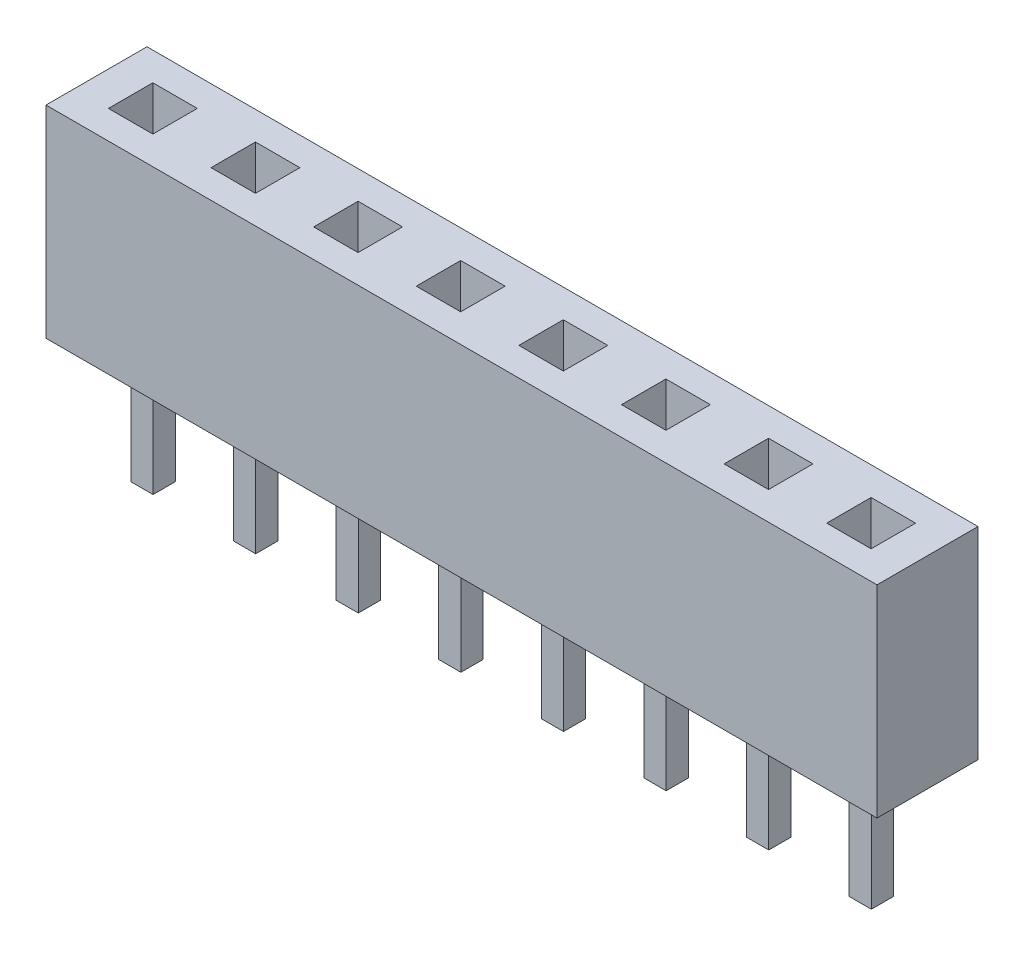
SolidWorks part; units mm, degrees
ref_plane "Front Plane" through (0, 0, 0) normal (0, 0, 1) x (1, 0, 0)
ref_plane "Top Plane" through (0, 0, 0) normal (0, 1, 0) x (1, 0, 0)
ref_plane "Right Plane" through (0, 0, 0) normal (1, 0, 0) x (0, 0, -1)
sketch "Sketch1" plane through (0, 0, 0) normal (0, 0, 1) x (1, 0, 0)
  line L1 (0, 0) -> (20.57, 0)
  line L2 (0, 0) -> (0, 5)
  line L3 (0, 5) -> (20.57, 5)
  line L4 (20.57, 0) -> (20.57, 5)
  dimension "D1" = 5
  dimension "D2" = 20.57
extrude "Boss-Extrude1" add sketch "Sketch1" along normal mid plane 2.5
sketch "Sketch2" plane through (0, 0, 0) normal (0, -1, 0) x (1, 0, 0)
  line L0 (0, 0) -> (20.57, 0) construction
  line L1 (20.57, 1.25) -> (20.57, -1.25) construction
  line L2 (3.385, -0.55) -> (4.485, -0.55)
  line L3 (0.845, -0.55) -> (1.945, -0.55)
  line L4 (0.845, -0.55) -> (0.845, 0.55)
  line L5 (0.845, 0.55) -> (1.945, 0.55)
  line L6 (1.945, -0.55) -> (1.945, 0.55)
  line L7 (0.845, -0.55) -> (1.945, 0.55) construction
  line L8 (0.845, 0.55) -> (1.945, -0.55) construction
  line L9 (3.385, -0.55) -> (3.385, 0.55)
  line L10 (3.385, 0.55) -> (4.485, 0.55)
  line L11 (4.485, -0.55) -> (4.485, 0.55)
  line L12 (3.385, -0.55) -> (4.485, 0.55) construction
  line L13 (3.385, 0.55) -> (4.485, -0.55) construction
  line L14 (5.925, -0.55) -> (7.025, -0.55)
  line L15 (5.925, -0.55) -> (5.925, 0.55)
  line L16 (5.925, 0.55) -> (7.025, 0.55)
  line L17 (7.025, -0.55) -> (7.025, 0.55)
  line L18 (5.925, -0.55) -> (7.025, 0.55) construction
  line L19 (5.925, 0.55) -> (7.025, -0.55) construction
  line L20 (8.465, -0.55) -> (9.565, -0.55)
  line L21 (8.465, -0.55) -> (8.465, 0.55)
  line L22 (8.465, 0.55) -> (9.565, 0.55)
  line L23 (9.565, -0.55) -> (9.565, 0.55)
  line L24 (8.465, -0.55) -> (9.565, 0.55) construction
  line L25 (8.465, 0.55) -> (9.565, -0.55) construction
  line L26 (11.005, -0.55) -> (12.105, -0.55)
  line L27 (11.005, -0.55) -> (11.005, 0.55)
  line L28 (11.005, 0.55) -> (12.105, 0.55)
  line L29 (12.105, -0.55) -> (12.105, 0.55)
  line L30 (11.005, -0.55) -> (12.105, 0.55) construction
  line L31 (11.005, 0.55) -> (12.105, -0.55) construction
  line L32 (13.545, -0.55) -> (14.645, -0.55)
  line L33 (13.545, -0.55) -> (13.545, 0.55)
  line L34 (13.545, 0.55) -> (14.645, 0.55)
  line L35 (14.645, -0.55) -> (14.645, 0.55)
  line L36 (13.545, -0.55) -> (14.645, 0.55) construction
  line L37 (13.545, 0.55) -> (14.645, -0.55) construction
  line L38 (16.085, -0.55) -> (17.185, -0.55)
  line L39 (16.085, -0.55) -> (16.085, 0.55)
  line L40 (16.085, 0.55) -> (17.185, 0.55)
  line L41 (17.185, -0.55) -> (17.185, 0.55)
  line L42 (16.085, -0.55) -> (17.185, 0.55) construction
  line L43 (16.085, 0.55) -> (17.185, -0.55) construction
  line L44 (18.625, -0.55) -> (19.725, -0.55)
  line L45 (18.625, -0.55) -> (18.625, 0.55)
  line L46 (18.625, 0.55) -> (19.725, 0.55)
  line L47 (19.725, -0.55) -> (19.725, 0.55)
  line L48 (18.625, -0.55) -> (19.725, 0.55) construction
  line L49 (18.625, 0.55) -> (19.725, -0.55) construction
  line L78 (1.395, 0) -> (3.935, 0) construction
  point P5 (1.395, 0)
  point P12 (3.935, 0)
  point P17 (6.475, 0)
  point P22 (9.015, 0)
  point P27 (11.555, 0)
  point P32 (14.095, 0)
  point P37 (16.635, 0)
  point P42 (19.175, 0)
  dimension "D1" = 1.1
  dimension "D3" = 1.395
  dimension "D4" = 2.54
  dimension "D2" = 8
extrude "Cut-Extrude1" cut sketch "Sketch2" against normal through all contours L3 L6 L5 L4 | L2 L11 L10 L9 | L14 L17 L16 L15 | L20 L23 L22 L21 | L26 L29 L28 L27 | L32 L35 L34 L33 | L38 L41 L40 L39 | L44 L47 L46 L45 region at (3.935, 0, 0) region at (1.395, 0, 0) region at (6.475, 0, 0) region at (9.015, 0, 0) region at (11.555, 0, 0) region at (14.095, 0, 0) region at (16.635, 0, 0) region at (19.175, 0, 0)
sketch "Sketch3" plane through (0, 0, 0) normal (0, -1, 0) x (1, 0, 0)
  line L1 (0, 1.25) -> (20.57, 1.25)
  line L2 (0, 1.25) -> (0, -1.25)
  line L3 (0, -1.25) -> (20.57, -1.25)
  line L4 (20.57, 1.25) -> (20.57, -1.25)
extrude "Boss-Extrude2" add sketch "Sketch3" against normal blind 1
sketch "Sketch4" plane through (0, 0, 0) normal (0, -1, 0) x (1, 0, 0)
  line L0 (1.125, 0) -> (1.675, 0) construction
  line L1 (1.125, 0.275) -> (1.675, 0.275)
  line L2 (1.125, 0.275) -> (1.125, -0.275)
  line L3 (1.125, -0.275) -> (1.675, -0.275)
  line L4 (1.675, 0.275) -> (1.675, -0.275)
  line L5 (0, 0) -> (20.57, 0) construction
  line L6 (20.57, 1.25) -> (20.57, -1.25) construction
  line L7 (0, 1.25) -> (0, -1.25) construction
  line L8 (3.665, 0.275) -> (3.665, -0.275)
  line L9 (3.665, 0.275) -> (4.215, 0.275)
  line L10 (3.665, -0.275) -> (4.215, -0.275)
  line L11 (4.215, 0.275) -> (4.215, -0.275)
  line L12 (6.205, 0.275) -> (6.205, -0.275)
  line L13 (6.205, 0.275) -> (6.755, 0.275)
  line L14 (6.205, -0.275) -> (6.755, -0.275)
  line L15 (6.755, 0.275) -> (6.755, -0.275)
  line L16 (8.745, 0.275) -> (8.745, -0.275)
  line L17 (8.745, 0.275) -> (9.295, 0.275)
  line L18 (8.745, -0.275) -> (9.295, -0.275)
  line L19 (9.295, 0.275) -> (9.295, -0.275)
  line L20 (11.285, 0.275) -> (11.285, -0.275)
  line L21 (11.285, 0.275) -> (11.835, 0.275)
  line L22 (11.285, -0.275) -> (11.835, -0.275)
  line L23 (11.835, 0.275) -> (11.835, -0.275)
  line L24 (13.825, 0.275) -> (13.825, -0.275)
  line L25 (13.825, 0.275) -> (14.375, 0.275)
  line L26 (13.825, -0.275) -> (14.375, -0.275)
  line L27 (14.375, 0.275) -> (14.375, -0.275)
  line L28 (16.365, 0.275) -> (16.365, -0.275)
  line L29 (16.365, 0.275) -> (16.915, 0.275)
  line L30 (16.365, -0.275) -> (16.915, -0.275)
  line L31 (16.915, 0.275) -> (16.915, -0.275)
  line L32 (18.905, 0.275) -> (18.905, -0.275)
  line L33 (18.905, 0.275) -> (19.455, 0.275)
  line L34 (18.905, -0.275) -> (19.455, -0.275)
  line L35 (19.455, 0.275) -> (19.455, -0.275)
  line L52 (1.125, 0.275) -> (3.665, 0.275) construction
  point P6 (1.4, 0)
  dimension "D1" = 0.55
  dimension "D2" = 1.4
  dimension "D4" = 2.54
  dimension "D3" = 8
extrude "Boss-Extrude3" add sketch "Sketch4" along normal blind 3 separate body
ref_axis "Axis1" through (1.395, 0, 0) along (0, -1, 0)
ref_axis "Axis2" through (19.175, 0, 0) along (0, -1, 0)
